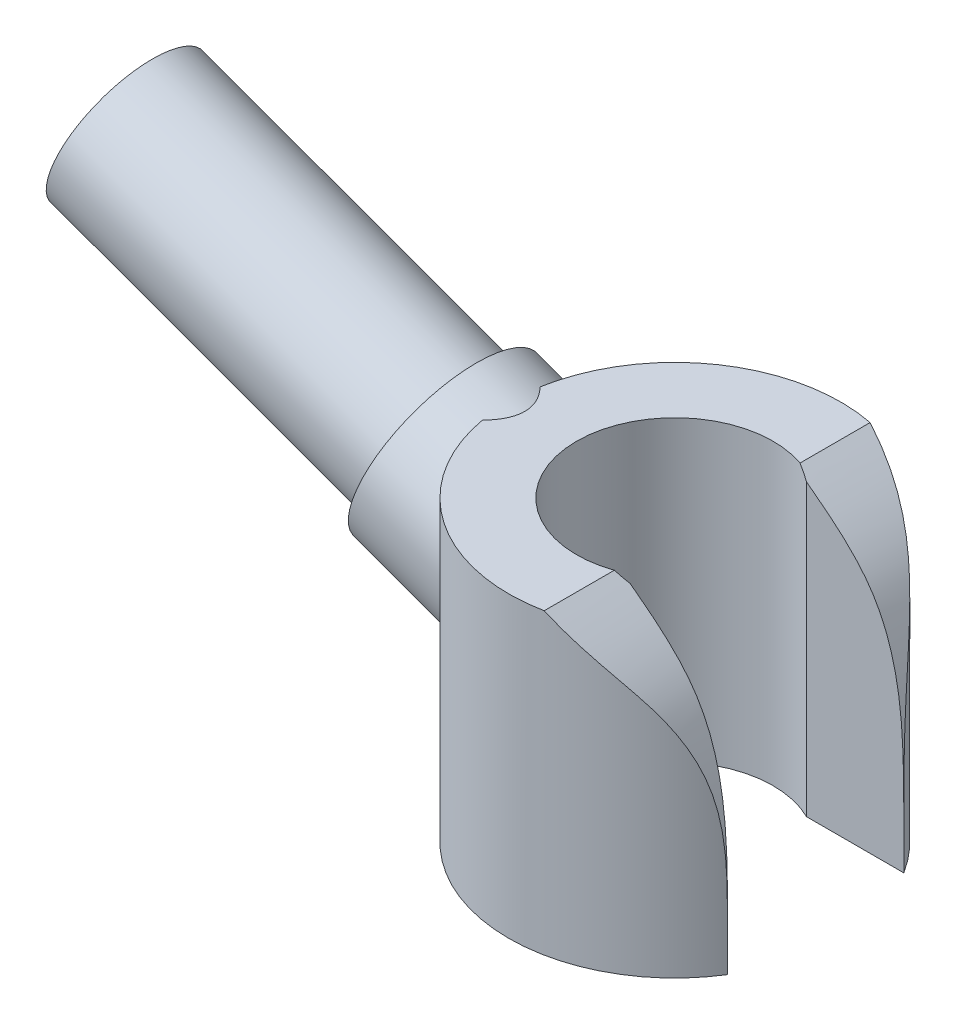
SolidWorks part; units mm, degrees
material "Yellow Plastic"
ref_plane "Front Plane" through (0, 0, 0) normal (0, 0, 1) x (1, 0, 0)
ref_plane "Top Plane" through (0, 0, 0) normal (0, 1, 0) x (1, 0, 0)
ref_plane "Right Plane" through (0, 0, 0) normal (1, 0, 0) x (0, 0, -1)
sketch "Sketch1" plane through (0, 0, 0) normal (0, 1, 0) x (1, 0, 0)
  line L0 (2.0767, -1.3) -> (0.6423, -1.3)
  line L1 (-2.45, 1.3) -> (2.45, 1.3) construction
  line L2 (-2.45, 1.3) -> (-2.45, -1.3) construction
  line L3 (-2.45, -1.3) -> (2.45, -1.3) construction
  line L4 (2.45, 1.3) -> (2.45, -1.3) construction
  line L5 (-2.45, 1.3) -> (2.45, -1.3) construction
  line L6 (-2.45, -1.3) -> (2.45, 1.3) construction
  line L7 (2.0767, 1.3) -> (0.6423, 1.3)
  arc A0 (2.0767, 1.3) -> (2.0767, -1.3) centre (0, 0) ccw
  arc A1 (0.6423, 1.3) -> (0.6423, -1.3) centre (0, 0) ccw
  dimension "D1" = 4.9
  dimension "D2" = 1
  dimension "D3" = 2.6
extrude "Extrude1" add sketch "Sketch1" along normal blind 4.4
ref_plane "Plane1" through (-2.45, 0, 0) normal (1, 0, 0) x (0, 0, -1)
sketch "Sketch11" plane through (0, 0, 0) normal (0, 0, 1) x (1, 0, 0)
  line L0 (2.0767, 4.4) -> (2.0767, 0) construction
  line L1 (2.0767, 4.4) -> (-2.45, 4.4) construction
  line L2 (0.4767, 4.4) -> (2.0767, 4.4)
  line L3 (2.0767, 4.4) -> (2.0767, 0.7)
  line L4 (-2.45, 0) -> (2.0767, 0) construction
  spline S0 degree 3 poles (2.0767, 0.7) (2.0756, 1.6922) (2.074, 3.2216) (0.8919, 4.0937) (0.4767, 4.4) knots 0 0 0 0 0.648765 1 1 1 1
  dimension "D1" = 0.5
  dimension "D2" = 1.6
  dimension "D3" = 1
  dimension "D4" = 0.7
extrude "Extrude5" cut sketch "Sketch11" against normal through all and the other way through all
sketch "Sketch14" plane through (-2.45, 0, 0) normal (1, 0, 0) x (0, 0, -1)
  line L0 (2.45, 4.4) -> (-2.45, 4.4) construction
  line L1 (1.35, 3.05) -> (-1.35, 3.05) construction
  circle A0 centre (0, 3.05) radius 1.35 construction
  point P4 (0, 4.4)
  dimension "D1" = 2.7
ref_plane "Plane3" through (-3.1437, 1.1442, 0) normal (0.9397, -0.342, 0) x (0, 0, -1)
sketch "Sketch15" plane through (-3.1437, 1.1442, 0) normal (0.9397, -0.342, 0) x (0, 0, -1)
  circle A0 centre (0, 2.0281) radius 1.35
  dimension "D1" = 2.7
extrude "Extrude6" add sketch "Sketch15" along normal up to surface and the other way blind 1 up to face at (0.4873, 1.816, -0.0064)
sketch "Sketch16" plane through (-4.0833, 1.4862, 0) normal (-0.9397, 0.342, 0) x (0, 0, 1)
  circle A0 centre (0, 2.0281) radius 1.12
  dimension "D1" = 2.24
extrude "Extrude7" add sketch "Sketch16" along normal blind 5
